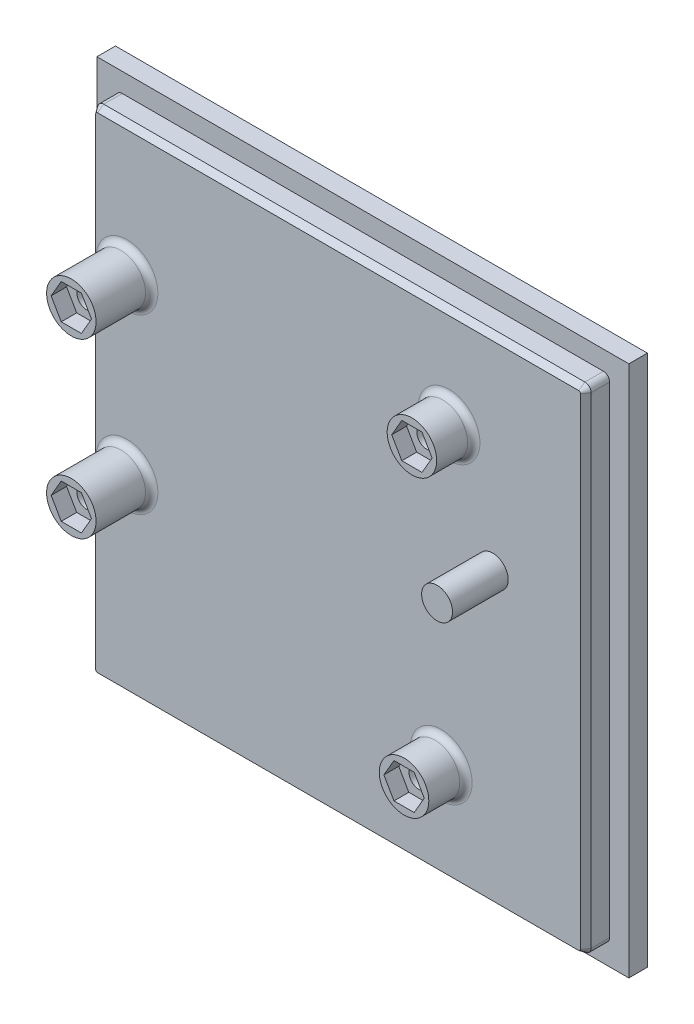
SolidWorks part; units mm, degrees
ref_plane "Front Plane" through (0, 0, 0) normal (0, 0, 1) x (1, 0, 0)
ref_plane "Top Plane" through (0, 0, 0) normal (0, 1, 0) x (1, 0, 0)
ref_plane "Right Plane" through (0, 0, 0) normal (1, 0, 0) x (0, 0, -1)
sketch "Sketch1" plane through (0, 0, 0) normal (0, 0, 1) x (1, 0, 0)
  line L1 (43, 43) -> (-43, 43)
  line L2 (43, 43) -> (43, -43)
  line L3 (43, -43) -> (-43, -43)
  line L4 (-43, 43) -> (-43, -43)
  line L5 (43, 43) -> (-43, -43) construction
  line L6 (43, -43) -> (-43, 43) construction
  point P0 (0, 0)
  dimension "D1" = 86
  dimension "D2" = 86
extrude "Boss-Extrude1" add sketch "Sketch1" along normal blind 3
sketch "Sketch2" plane through (0, 0, 3) normal (0, 0, 1) x (1, 0, 0)
  line L0 (43, -43) -> (43, 43) construction
  line L1 (-43, -43) -> (43, -43) construction
  line L2 (-43, 43) -> (-43, -43) construction
  line L3 (43, 43) -> (-43, 43) construction
  line L4 (43, -43) -> (43, 43)
  line L5 (-43, -43) -> (43, -43)
  line L6 (-43, 43) -> (-43, -43)
  line L7 (43, 43) -> (-43, 43)
  line L8 (39.9, 39.9) -> (-39.9, 39.9)
  line L9 (-39.9, 39.9) -> (-39.9, -39.9)
  line L10 (-39.9, -39.9) -> (39.9, -39.9)
  line L11 (39.9, -39.9) -> (39.9, 39.9)
  dimension "D1" = 3.1
extrude "Boss-Extrude2" add sketch "Sketch2" along normal blind 4 contours L10 L11 L8 L9 region at (0, 0, 3)
sketch "Sketch3" plane through (0, 0, 7) normal (0, 0, 1) x (1, 0, 0)
  line L0 (43, 43) -> (-43, 43) construction
  line L1 (-43, 43) -> (-43, -43) construction
  line L2 (43, -43) -> (43, 43) construction
  line L3 (-43, -43) -> (43, -43) construction
  circle A0 centre (-34.14, 18.82) radius 4
  circle A1 centre (-34.14, -9.12) radius 4
  circle A2 centre (17.93, 23.9) radius 4
  circle A3 centre (16.66, -24.36) radius 4
  dimension "D1" = 8
  dimension "D2" = 8
  dimension "D3" = 8
  dimension "D4" = 8
  dimension "D5" = 24.18
  dimension "D6" = 8.86
  dimension "D7" = 27.94
  dimension "D8" = 8.86
  dimension "D9" = 25.07
  dimension "D10" = 19.1
  dimension "D11" = 26.34
  dimension "D12" = 18.64
extrude "Boss-Extrude3" add sketch "Sketch3" along normal blind 9 contours A0 | A1 region at (-34.14, 18.82, 7) region at (-34.14, -9.12, 7)
extrude "Boss-Extrude4" add sketch "Sketch5<3>" along normal blind 6 contours A2 | A3 region at (17.93, 23.9, 7) region at (16.66, -24.36, 7)
sketch "Sketch5<3>" plane through (0, 0, 7) normal (0, 0, 1) x (1, 0, 0) same geometry as "Sketch3"
fillet "Fillet1" radius 1 8 edges at (39.9, 39.9, 5) (39.9, -39.9, 5) (-39.9, -39.9, 5) (-39.9, 39.9, 5) (-30.14, 18.82, 7) (-30.14, -9.12, 7) (21.93, 23.9, 7) (20.66, -24.36, 7)
sketch "Sketch4" plane through (0, 0, 13) normal (0, 0, 1) x (1, 0, 0)
  line L1 (13.398, -24.36) -> (15.029, -27.185)
  line L2 (15.029, -27.185) -> (18.291, -27.185)
  line L3 (18.291, -27.185) -> (19.922, -24.36)
  line L4 (19.922, -24.36) -> (18.291, -21.535)
  line L5 (18.291, -21.535) -> (15.029, -21.535)
  line L6 (15.029, -21.535) -> (13.398, -24.36)
  line L7 (14.668, 23.9) -> (16.299, 21.075)
  line L8 (16.299, 21.075) -> (19.561, 21.075)
  line L9 (19.561, 21.075) -> (21.192, 23.9)
  line L10 (21.192, 23.9) -> (19.561, 26.725)
  line L11 (19.561, 26.725) -> (16.299, 26.725)
  line L12 (16.299, 26.725) -> (14.668, 23.9)
  circle A0 centre (16.66, -24.36) radius 2.825 construction
  circle A1 centre (17.93, 23.9) radius 2.825 construction
  dimension "D1" = 5.65
  dimension "D2" = 5.65
extrude "Cut-Extrude1" cut sketch "Sketch4" against normal blind 2.4
sketch "Sketch5" plane through (0, 0, 10.6) normal (0, 0, 1) x (1, 0, 0)
  circle A0 centre (17.93, 23.9) radius 1.6
  circle A1 centre (16.66, -24.36) radius 1.6
  dimension "D1" = 3.2
  dimension "D2" = 3.2
extrude "Cut-Extrude2" cut sketch "Sketch5" against normal up to surface (3.6 mm away) up to face at (-29.14, 18.82, 7)
sketch "Sketch6" plane through (0, 0, 16) normal (0, 0, 1) x (1, 0, 0)
  line L1 (-37.402, 18.82) -> (-35.771, 15.995)
  line L2 (-35.771, 15.995) -> (-32.509, 15.995)
  line L3 (-32.509, 15.995) -> (-30.878, 18.82)
  line L4 (-30.878, 18.82) -> (-32.509, 21.645)
  line L5 (-32.509, 21.645) -> (-35.771, 21.645)
  line L6 (-35.771, 21.645) -> (-37.402, 18.82)
  line L7 (-37.402, -9.12) -> (-35.771, -11.945)
  line L8 (-35.771, -11.945) -> (-32.509, -11.945)
  line L9 (-32.509, -11.945) -> (-30.878, -9.12)
  line L10 (-30.878, -9.12) -> (-32.509, -6.295)
  line L11 (-32.509, -6.295) -> (-35.771, -6.295)
  line L12 (-35.771, -6.295) -> (-37.402, -9.12)
  circle A0 centre (-34.14, 18.82) radius 2.825 construction
  circle A1 centre (-34.14, -9.12) radius 2.825 construction
  dimension "D1" = 5.65
  dimension "D2" = 5.65
extrude "Cut-Extrude3" cut sketch "Sketch6" against normal blind 2.5
sketch "Sketch7" plane through (0, 0, 13.5) normal (0, 0, 1) x (1, 0, 0)
  circle A0 centre (-34.14, 18.82) radius 1.6
  circle A1 centre (-34.14, -9.12) radius 1.6
  dimension "D1" = 3.2
  dimension "D2" = 3.2
extrude "Cut-Extrude4" cut sketch "Sketch7" against normal blind 6
sketch "Sketch8" plane through (0, 0, 7) normal (0, 0, 1) x (1, 0, 0)
  line L0 (43, -43) -> (43, 43) construction
  line L2 (-43, -43) -> (43, -43) construction
  circle A0 centre (25, 7) radius 2.5
  dimension "D1" = 5
  dimension "D2" = 18
  dimension "D3" = 50
extrude "Boss-Extrude5" add sketch "Sketch8" along normal blind 9
chamfer "Chamfer1" distance 1 angle 35 8 edges at (-39.9, 0, 7) (0, 39.9, 7) (-39.6071, 39.6071, 7) (39.6071, 39.6071, 7) (39.9, 0, 7) (-39.6071, -39.6071, 7) (39.6071, -39.6071, 7) (0, -39.9, 7) first distance on face at (-39.9, 0, 5) first distance on face at (0, 39.9, 5) first distance on face at (-39.5036, 39.5036, 5) first distance on face at (39.5036, 39.5036, 5) first distance on face at (39.9, 0, 5) first distance on face at (-39.5036, -39.5036, 5) first distance on face at (39.5036, -39.5036, 5) first distance on face at (0, -39.9, 5)
